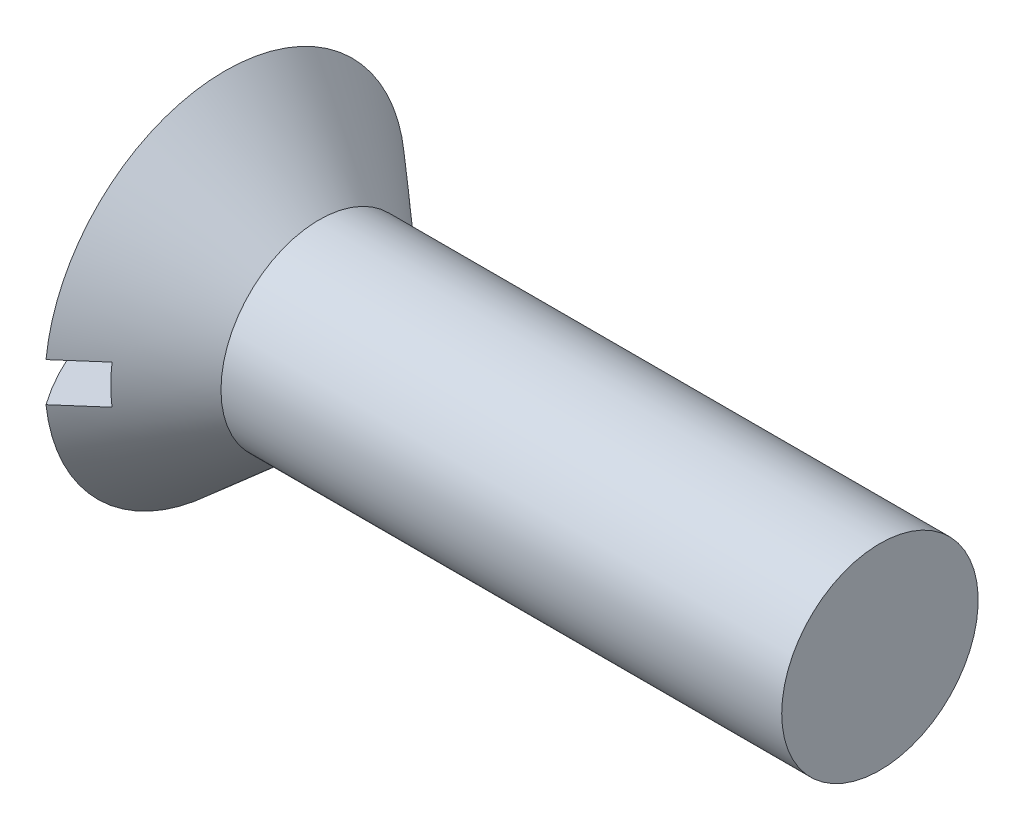
SolidWorks part; units mm, degrees
revolve "Base-Revolve" add sketch "BodySke" angle 360 about L4
sketch "BodySke" plane through (0, 0, 0) normal (0, 0, 1) x (1, 0, 0)
  line L0 (0, 0) -> (69.0502, 0)
  line L1 (69.0502, 0) -> (69.0502, 9.525)
  line L2 (69.0502, 9.525) -> (14.6812, 9.525)
  line L3 (5.5502, -17.4625) -> (14.6812, -9.525) construction
  line L4 (-15.875, 0) -> (82.55, 0) construction
  line L5 (5.5502, 17.4625) -> (14.6812, 9.525)
  line L6 (15.4749, 12.7) -> (15.475, -3.175) construction
  line L7 (37.3002, 12.7) -> (37.3002, -3.175) construction
  arc A0 (0, 0) -> (5.5502, 17.4625) centre (30.2463, 0) cw
  dimension "Length" = 63.5
  dimension "Diameter" = 19.05
  dimension "Head_dia" = 34.925
cosmetic thread "ThreadCosmetic" [suppressed] parameters "Thread_length"=31.75, "Thread_minor"=16.0274
extrude "Slot" cut sketch "Sketch2" along normal blind 8.9662
sketch "Sketch2" plane through (0, 0, 0) normal (1, 0, 0) x (0, 0, -1)
  line L0 (17.4625, -1.8923) -> (-17.4625, -1.8923)
  line L1 (17.4625, -1.8923) -> (17.4625, 1.8923)
  line L2 (-17.4625, 1.8923) -> (17.4625, 1.8923)
  line L3 (-17.4625, 1.8923) -> (-17.4625, -1.8923)
  dimension "D1" = 34.925
  dimension "D3" = 17.4625
  dimension "D4" = 1.8923
ref_plane "Plane1" through (0, 0, 0) normal (0, 0, 1) x (1, 0, 0)
ref_plane "Plane2" through (0, 0, 0) normal (0, 1, 0) x (1, 0, 0)
ref_plane "Plane3" through (0, 0, 0) normal (1, 0, 0) x (0, 0, -1)
sketch "Sketch3" plane through (0, 0, 0) normal (1, 0, 0) x (0, 0, -1)
  line L0 (1.3208, -8.3312) -> (-1.3208, -8.3312)
  line L1 (1.3208, -8.3312) -> (1.3208, 8.3312)
  line L2 (-1.3208, 8.3312) -> (1.3208, 8.3312)
  line L3 (-1.3208, 8.3312) -> (-1.3208, -8.3312)
  dimension "D1" = 1.3208
  dimension "D2" = 8.3312
ref_plane "Plane4" through (10.16, 0, 0) normal (1, 0, 0) x (0, 0, -1)
sketch "Sketch4" plane through (10.16, 0, 0) normal (1, 0, 0) x (0, 0, -1)
  line L0 (0.6604, -0.6604) -> (-0.6604, -0.6604)
  line L1 (0.6604, -0.6604) -> (0.6604, 0.6604)
  line L2 (-0.6604, 0.6604) -> (0.6604, 0.6604)
  line L3 (-0.6604, 0.6604) -> (-0.6604, -0.6604)
  dimension "D1" = 1.3208
  dimension "D2" = 1.3208
  dimension "D3" = 0.6604
  dimension "D4" = 0.6604
loft "Cross" cut profiles "Sketch3", "Sketch4"
pattern_circular "CirPattern1" count 2 every 90 about axis through (-15.875, 0, 0) along (1, 0, 0) of "Cross"
sketch "ThdSchSke" plane through (0, 0, 0) normal (0, 0, 1) x (1, 0, 0)
  line L0 (37.3002, -8.0137) -> (36.242, -9.525)
  line L1 (37.3002, -8.0137) -> (38.3584, -9.525)
  line L2 (38.3584, -9.525) -> (38.3584, -11.9062)
  line L3 (-3.175, 0) -> (5.1513, 0) construction
  line L4 (5.5502, 17.4625) -> (5.5502, 1.8923) construction
  line L5 (38.3584, -11.9062) -> (36.242, -11.9063)
  line L6 (36.242, -11.9063) -> (36.242, -9.525)
  dimension "Diameter" = 19.05
  dimension "Thread_minor" = 16.0274
  dimension "Start" = 31.75
revolve "ThreadSchematic" [suppressed] cut sketch "ThdSchSke" angle 360 about L3
pattern_linear "ThdSchPat" [suppressed]
equation "\"D1@Sketch2\" = \"Head_dia@BodySke\""
equation "\"D3@Sketch2\" = \"D1@Sketch2\" / 2"
equation "\"D4@Sketch2\" = \"Slot_width@Sketch2\" / 2"
equation "\"D1@Sketch3\" = \"Cross_width@Sketch3\" / 2"
equation "\"D2@Sketch3\" = \"Cross_dia@Sketch3\" / 2"
equation "\"D1@Sketch4\" = \"Cross_width@Sketch3\"*.5"
equation "\"D2@Sketch4\" = \"D1@Sketch4\""
equation "\"D3@Sketch4\" = \"D1@Sketch4\" / 2"
equation "\"D4@Sketch4\" = \"D2@Sketch4\" / 2"
equation "\"Thread_length@ThreadCosmetic\" = ((sgn( (\"Length@BodySke\" - \"Advance@BodySke\" - ( ( ( \"Head_dia@BodySke\" - \"Diameter@BodySke\" ) * 0.5 ) / tan( \"Head_ang@BodySke\" * 0.008726646 ) ) ) - \"Thread_nom@BodySke\" )-1)*( (\"Length@BodySke\" - \"Advance@BodySke\" - ( ( ( \"Head_dia@BodySke\" - \"Diameter@BodySke\" ) * 0.5 ) / tan( \"Head_ang@BodySke\" * 0.008726646 ) ) ) - \"Thread_nom@BodySke\" ))/-2+ \"Thread_nom@BodySke\""
equation "\"Thread_minor@ThdSchSke\" = \"Thread_minor@ThreadCosmetic\""
equation "\"Diameter@ThdSchSke\" = \"Diameter@BodySke\""
equation "\"Overcut@ThdSchSke\" = \"Diameter@BodySke\" * 1.25"
equation "\"Start@ThdSchSke\" = 0.000001 + \"Length@BodySke\" - \"Thread_length@ThreadCosmetic\"  '---Countersunk---"
equation "\"Num_threads@ThdSchPat\" = int( \"Thread_length@ThreadCosmetic\" / \"Advance@BodySke\" + 0.999 )  + 1"
equation "\"Advance@ThdSchPat\" = \"Thread_length@ThreadCosmetic\" /  (\"Num_threads@ThdSchPat\" - 1) 'relax it"
